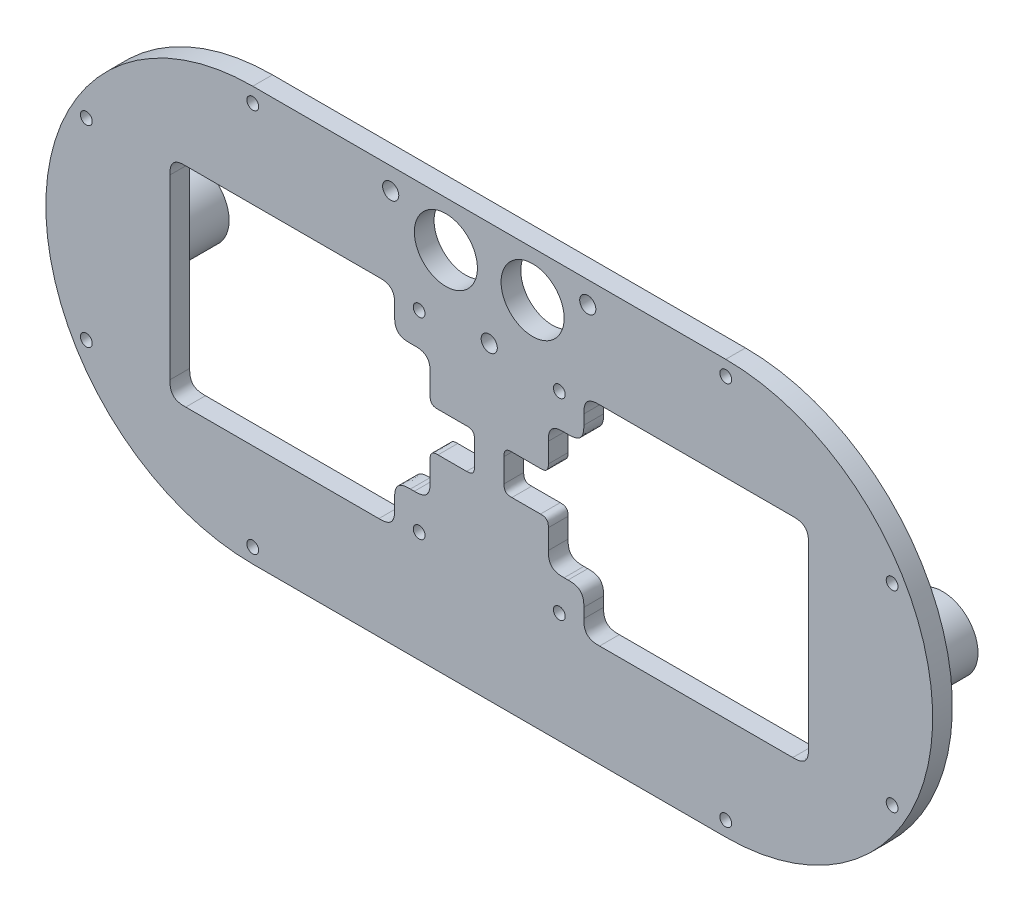
SolidWorks part; units mm, degrees
ref_plane "Front Plane" through (0, 0, 0) normal (0, 0, 1) x (1, 0, 0)
ref_plane "Top Plane" through (0, 0, 0) normal (0, 1, 0) x (1, 0, 0)
ref_plane "Right Plane" through (0, 0, 0) normal (1, 0, 0) x (0, 0, -1)
sketch "Sketch1" plane through (0, 0, 0) normal (0, 0, 1) x (1, 0, 0)
  line L0 (-60, 0) -> (0, 0) construction
  line L1 (0, -11) -> (0, 11) construction
  line L2 (-60, 52.5) -> (60, 52.5)
  line L3 (-60, -52.5) -> (60, -52.5)
  line L5 (-24, 26.5) -> (-81, 26.5)
  line L6 (-24, 26.5) -> (-24, -26.5)
  line L7 (-24, -26.5) -> (-81, -26.5)
  line L8 (-81, 26.5) -> (-81, -26.5)
  line L9 (-24, 26.5) -> (-81, -26.5) construction
  line L10 (-24, -26.5) -> (-81, 26.5) construction
  line L12 (24, -26.5) -> (81, -26.5)
  line L13 (81, 26.5) -> (81, -26.5)
  line L14 (24, 26.5) -> (81, 26.5)
  line L15 (24, 26.5) -> (24, -26.5)
  arc A0 (-60, 52.5) -> (-60, -52.5) centre (-60, 0) ccw
  circle A1 centre (-60, 0) radius 48.75 construction
  arc A18 (60, 52.5) -> (60, -52.5) centre (60, 0) cw
  arc A19 (-7.5, 0) -> (-60, 52.5) centre (-60, 0) ccw construction
  arc A20 (-60, -52.5) -> (-7.5, 0) centre (-60, 0) ccw construction
  arc A21 (60, -52.5) -> (60, 52.5) centre (60, 0) cw construction
  circle A22 centre (-60, 48.75) radius 1.5
  circle A23 centre (-17.7813, 24.375) radius 1.5
  circle A24 centre (-17.7813, -24.375) radius 1.5
  circle A25 centre (-60, -48.75) radius 1.5
  circle A26 centre (-102.2187, -24.375) radius 1.5
  circle A27 centre (-102.2187, 24.375) radius 1.5
  circle A28 centre (102.2187, 24.375) radius 1.5
  circle A29 centre (102.2187, -24.375) radius 1.5
  circle A30 centre (60, -48.75) radius 1.5
  circle A31 centre (17.7813, -24.375) radius 1.5
  circle A32 centre (17.7813, 24.375) radius 1.5
  circle A33 centre (60, 48.75) radius 1.5
  point P1 (-52.5, 0)
  point P20 (-60, 0)
  point P21 (-60, 0)
  dimension "D1" = 105
  dimension "D2" = 97.5
  dimension "D4" = 3
  dimension "D3" = 60
  dimension "D6" = 21
  dimension "D7" = 53
  dimension "D8" = 57
  dimension "D5" = 6
extrude "Boss-Extrude1" add sketch "Sketch1" along normal blind 5 contours A18 L2 A0 L3 A27 A26 A25 A24 A23 A22 region at (0, 0, 0)
sketch "Sketch3" plane through (0, 0, 0) normal (0, 0, -1) x (-1, 0, 0)
  line L0 (0, 11) -> (0, -11) construction
  circle A0 centre (-95, 0) radius 9
  circle A1 centre (-95, 0) radius 6
  circle A2 centre (95, 0) radius 9
  circle A3 centre (95, 0) radius 6
  dimension "D1" = 18
  dimension "D3" = 12
  dimension "D2" = 95
extrude "Boss-Extrude3" add sketch "Sketch3" along normal blind 15
fillet "Fillet2" radius 5 2 edges at (104, 0, 0) (-86, 0, 0) curvature continuous yes
sketch "Sketch4" plane through (0, 0, 5) normal (0, 0, 1) x (1, 0, 0)
  line L0 (0, 16) -> (0, -16) construction
  line L1 (-24, 16) -> (24, 16)
  line L2 (-24, 26.5) -> (-24, -26.5) construction
  line L3 (24, 26.5) -> (24, -26.5) construction
  line L4 (-24, -16) -> (24, -16)
  line L5 (24, 26.5) -> (24, -26.5)
  line L6 (-15, 16) -> (15, 16)
  line L7 (-15, 16) -> (-15, -16)
  line L8 (-15, -16) -> (15, -16)
  line L9 (15, 16) -> (15, -16)
  line L10 (-15, 16) -> (15, -16) construction
  line L11 (-15, -16) -> (15, 16) construction
  line L12 (-24, 26.5) -> (-24, -26.5)
  point P4 (0, 0)
  point P13 (0, 0)
  line M14 (24, -26.5) -> (24, 26.5)
  line M20 (-24, 26.5) -> (-24, -26.5)
  dimension "D1" = 32
  dimension "D2" = 30
extrude "Cut-Extrude1" cut sketch "Sketch4" against normal blind 15 contours L7 L1 L4 M20 | L1 L9 L4 M14 region at (-19.5, 0, 5) region at (19.5, 0, 5)
fillet "Fillet3" radius 4 16 edges at (24, -16, 2.5) (24, -26.5, 2.5) (81, -26.5, 2.5) (81, 26.5, 2.5) (24, 26.5, 2.5) (24, 16, 2.5) (15, 16, 2.5) (15, -16, 2.5) (-81, -26.5, 2.5) (-24, -26.5, 2.5) (-24, -16, 2.5) (-15, -16, 2.5) (-15, 16, 2.5) (-24, 16, 2.5) (-24, 26.5, 2.5) (-81, 26.5, 2.5) curvature continuous yes
sketch "Sketch6" plane through (0, 0, 0) normal (0, 0, -1) x (-1, 0, 0)
  line L0 (0, 61.2487) -> (0, -60.5803) construction
  line L1 (-60, 48.75) -> (-60, -48.75) construction
  line L2 (60, 48.75) -> (60, -48.75) construction
  circle A0 centre (-60, 0) radius 52.5
  circle A1 centre (-11, 41) radius 8
  circle A2 centre (11, 41) radius 8
  circle A3 centre (11, 41) radius 10
  circle A4 centre (-11, 41) radius 10
  circle A5 centre (60, 0) radius 52.5
  circle A6 centre (0, 26) radius 2.05
  circle A7 centre (25, 47) radius 2.05
  circle A8 centre (-25, 47) radius 2.05
  point P27 (-25, 47.6332)
  point P28 (0, 26.7742)
  point P29 (-11, 40.2286)
  dimension "D1" = 16
  dimension "D2" = 105
  dimension "D3" = 20
  dimension "D4" = 20
  dimension "D5" = 105
  dimension "D6" = 4.1
  dimension "D7" = 4.1
  dimension "D8" = 25
  dimension "D9" = 15
  dimension "D10" = 11
  dimension "D11" = 6
  dimension "D12" = 41
extrude "Cut-Extrude2" cut sketch "Sketch6" against normal blind 10 contours A8 | A7 | A6 | A1 | A2 region at (11, 41, 0) region at (-11, 41, 0) region at (0, 26, 0) region at (-25, 47, 0) region at (25, 47, 0)
sketch "Sketch7" plane through (0, 0, 5) normal (0, 0, 1) x (1, 0, 0)
  line L0 (-11.25, 5) -> (-17.3787, 5)
  line L1 (-11.25, 5) -> (-3.75, 5)
  line L2 (-11.25, 5) -> (-11.25, -5) construction
  line L3 (-11.25, -5) -> (-3.75, -5)
  line L4 (-3.75, 5) -> (-3.75, -5)
  line L5 (-7.5, 0) -> (-3.75, -5) construction
  line L6 (-11.25, -5) -> (-7.5, 0) construction
  line L7 (-17.3787, 5) -> (-17.3787, -5)
  line L8 (-17.3787, -5) -> (-11.25, -5)
  line L9 (-7.5, 0) -> (-3.75, 5) construction
  line L10 (-11.25, 5) -> (-7.5, 0) construction
  line L11 (0, -11.0275) -> (0, 11.0275) construction
  line L12 (17.3787, -5) -> (11.25, -5)
  line L13 (3.75, 5) -> (3.75, -5)
  line L14 (11.25, -5) -> (3.75, -5)
  line L15 (11.25, 5) -> (3.75, 5)
  line L16 (11.25, 5) -> (17.3787, 5)
  line L17 (17.3787, 5) -> (17.3787, -5)
  arc A0 (-60, 52.5) -> (-60, -52.5) centre (-60, 0) ccw construction
  arc A1 (-60, 52.5) -> (-60, -52.5) centre (-60, 0) ccw construction
  arc A2 (-60, 52.5) -> (-60, -52.5) centre (-60, 0) ccw construction
  arc A3 (-7.5, 0) -> (-7.7386, 5) centre (-60, 0) ccw construction
  arc A4 (-7.7386, -5) -> (-7.5, 0) centre (-60, 0) ccw construction
  arc A5 (-7.7386, 5) -> (-60, 52.5) centre (-60, 0) ccw construction
  arc A6 (-60, -52.5) -> (-7.7386, -5) centre (-60, 0) ccw construction
  point P4 (-7.5, 0)
  dimension "D1" = 10
  dimension "D2" = 7.5
extrude "Cut-Extrude3" cut sketch "Sketch7" against normal up to surface (5 mm away) up to face at (3, 41, 0)
fillet "Fillet4" radius 2 8 edges at (-15, -5, 2.5) (-3.75, 5, 2.5) (-15, 5, 2.5) (-3.75, -5, 2.5) (15, -5, 2.5) (3.75, -5, 2.5) (15, 5, 2.5) (3.75, 5, 2.5) curvature continuous yes
